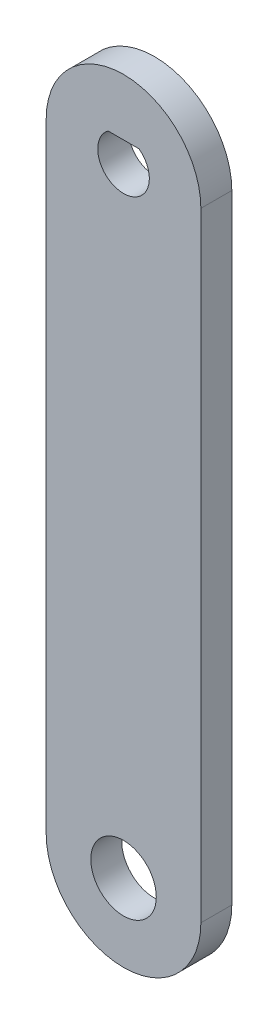
SolidWorks part; units mm, degrees
material "Balsa"
ref_plane "Alzado" through (0, 0, 0) normal (0, 0, 1) x (1, 0, 0)
ref_plane "Planta" through (0, 0, 0) normal (0, 1, 0) x (1, 0, 0)
ref_plane "Vista lateral" through (0, 0, 0) normal (1, 0, 0) x (0, 0, -1)
sketch "Croquis1" plane through (0, 0, 0) normal (0, 0, 1) x (1, 0, 0)
  line L0 (0, 0) -> (0, -60) construction
  line L1 (7.5, 0) -> (7.5, -60)
  line L2 (-7.5, 0) -> (-7.5, -60)
  line L3 (-1.5, 2) -> (1.5, 2)
  arc A0 (7.5, 0) -> (-7.5, 0) centre (0, 0) ccw
  arc A1 (-7.5, -60) -> (7.5, -60) centre (0, -60) ccw
  arc A2 (-1.5, 2) -> (1.5, 2) centre (0, 0) ccw
  circle A3 centre (0, -60) radius 3.175
  point P3 (0, -30)
  dimension "D3" = 5
  dimension "D1" = 60
  dimension "D2" = 15
  dimension "D4" = 3
extrude "Saliente-Extruir1" add sketch "Croquis1" along normal blind 1.5 and the other way blind 1.5
equation "\"L\"= 60"
equation "\"D1@Croquis1\"=\"L\""
equation "\"g\"=15"
equation "\"D2@Croquis1\"=\"g\""
equation "\"d\"= 6.35"
equation "\"D5@Croquis1\"=\"d\""
